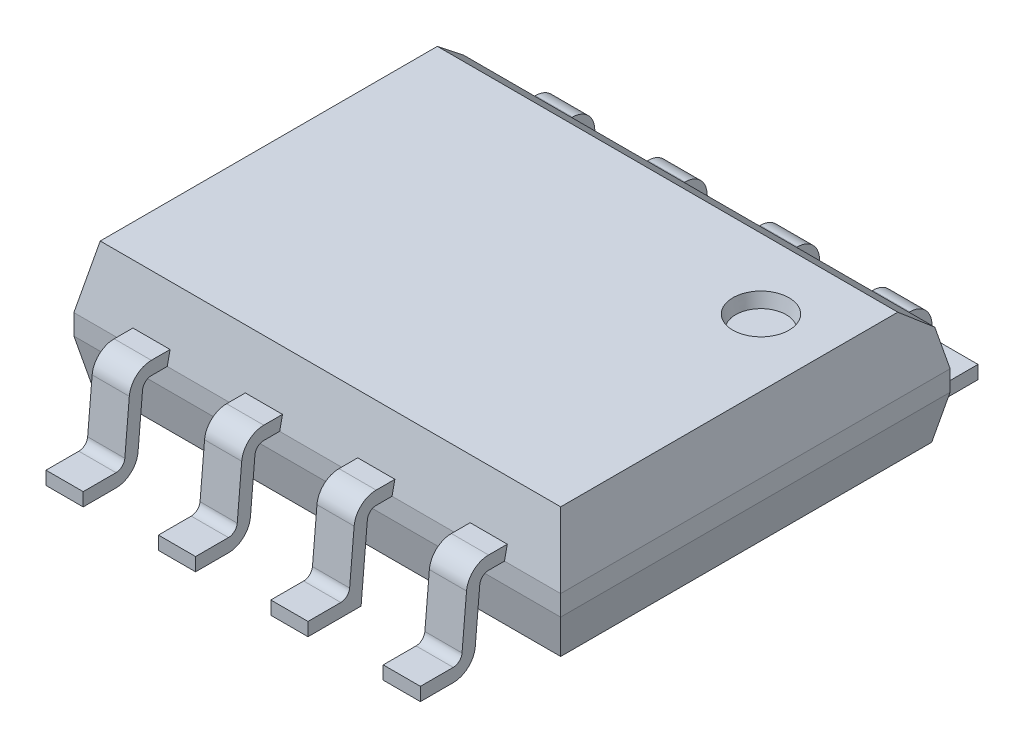
SolidWorks part; units mm, degrees
note: '?' marks a value the reader was unsure of.
ref_plane "Front Plane" through (0, 0, 0) normal (0, 0, 1) x (1, 0, 0)
ref_plane "Top Plane" through (0, 0, 0) normal (0, 1, 0) x (1, 0, 0)
ref_plane "Right Plane" through (0, 0, 0) normal (1, 0, 0) x (0, 0, -1)
ref_axis "Axis1" through (3.025, 0, 0) along (-1, 0, 0)?
sketch "Sketch1" plane through (0, 0, 0) normal (0, 1, 0) x (1, 0, 0)
  line L1 (-2.75, 2.2) -> (2.75, 2.2)
  line L2 (-2.75, 2.2) -> (-2.75, -2.2)
  line L3 (-2.75, -2.2) -> (2.75, -2.2)
  line L4 (2.75, 2.2) -> (2.75, -2.2)
  dimension "D1" = 5.5
  dimension "D2" = 4.4
  dimension "D3" = 2.75
  dimension "D4" = 2.2
extrude "Extrude1" add sketch "Sketch1" along normal blind 0.7 draft 12 and the other way blind 0.23
sketch "Sketch2" plane through (0, -0.23, 0) normal (0, -1, 0) x (1, 0, 0)
  line L4 (-2.75, 2.2) -> (-2.75, -2.2)
  line L5 (-2.75, -2.2) -> (2.75, -2.2)
  line L6 (2.75, -2.2) -> (2.75, 2.2)
  line L7 (2.75, 2.2) -> (-2.75, 2.2)
  line L8 (-2.75, 2.2) -> (-2.75, -2.2)
  line L9 (-2.75, -2.2) -> (2.75, -2.2)
  line L10 (2.75, -2.2) -> (2.75, 2.2)
  line L11 (2.75, 2.2) -> (-2.75, 2.2)
  dimension "D1" = 0
extrude "Extrude2" add sketch "Sketch2" along normal blind 0.49 draft 12
chamfer "Chamfer1" distance 0.3 angle 38.5 1 edges at (0, 0.7, -2.0512)
sketch "Sketch3" plane through (0, 0.7, 0) normal (0, 1, 0) x (-1, 0, 0)
  circle A0 centre (-1.8453, -0.9674) radius 0.3175
extrude "Cut-Extrude1" cut sketch "Sketch3" against normal blind 0.15 draft 12
sketch "Sketch4" plane through (0, 0, 0) normal (1, 0, 0) x (0, 0, -1)
  line L0 (0, 0.15) -> (0, 0)
  line L1 (-2.6874, -0.75) -> (-2.6087, 0.15)
  line L2 (-2.4713, 0) -> (2.4713, 0)
  line L3 (2.4713, 0) -> (2.55, -0.9)
  line L4 (-3.15, -0.75) -> (-2.6874, -0.75)
  line L5 (2.55, -0.9) -> (3.15, -0.9)
  line L6 (3.15, -0.9) -> (3.15, -0.75)
  line L7 (3.15, -0.75) -> (2.6874, -0.75)
  line L8 (2.6874, -0.75) -> (2.6087, 0.15)
  line L9 (2.6087, 0.15) -> (-2.6087, 0.15)
  line L10 (-3.15, -0.9) -> (-3.15, -0.75)
  line L11 (-2.55, -0.9) -> (-3.15, -0.9)
  line L12 (-2.4713, 0) -> (-2.55, -0.9)
  line L13 (2.2, 0) -> (-2.2, 0) construction
  line L14 (-2.0958, -0.72) -> (2.0958, -0.72) construction
  dimension "D1" = 0.15
  dimension "D2" = 0.15
  dimension "D3" = 0.15
  dimension "D4" = 0.6
  dimension "D5" = 6.3
  dimension "D6" = 95
  dimension "D7" = 0.18
extrude "Extrude3" add sketch "Sketch4" along normal blind 0.21 and the other way blind 0.21 from offset 0.635 contours L8 L9 L1 L4 L10 L11 L12 L2 L3 L5 L6 L7
pattern_linear "LPattern3" count 2 spacing 1.27 along (1, 0, 0) count 3 spacing 1.27 along (-1, 0, 0) of "Extrude3"
fillet "Fillet1" radius 0.1 16 edges at (1.905, -0.75, 2.6874) (0.635, -0.75, 2.6874) (-0.635, -0.75, 2.6874) (-1.905, -0.75, 2.6874) (1.905, 0, 2.4713) (0.635, 0, 2.4713) (-0.635, 0, 2.4713) (-1.905, 0, 2.4713) (1.905, -0.75, -2.6874) (0.635, -0.75, -2.6874) (-0.635, -0.75, -2.6874) (1.905, 0, -2.4713) (0.635, 0, -2.4713) (-0.635, 0, -2.4713) (-1.905, 0, -2.4713) (-1.905, -0.75, -2.6874)
fillet "Fillet2" radius 0.25 15 edges at (1.905, -0.9, 2.55) (1.905, 0.15, 2.6087) (-0.635, 0.15, 2.6087) (0.635, 0.15, 2.6087) (-0.635, -0.9, 2.55) (-1.905, -0.9, 2.55) (-1.905, 0.15, 2.6087) (1.905, 0.15, -2.6087) (0.635, 0.15, -2.6087) (-0.635, 0.15, -2.6087) (-1.905, 0.15, -2.6087) (1.905, -0.9, -2.55) (0.635, -0.9, -2.55) (-0.635, -0.9, -2.55) (-1.905, -0.9, -2.55)
ref_plane "Plane1" through (0, -0.9, 0) normal (0, 1, 0) x (-1, 0, 0)
sketch "Component_Outline" plane through (0, -0.9, 0) normal (0, 1, 0) x (-1, 0, 0)
  line L0 (2.115, 3.15) -> (2.115, 2.2)
  line L1 (-1.695, -3.15) -> (-2.115, -3.15)
  line L2 (1.695, 3.15) -> (1.695, 2.2)
  line L3 (1.695, 2.2) -> (0.845, 2.2)
  line L4 (0.845, 3.15) -> (0.845, 2.2)
  line L5 (-0.425, -3.15) -> (-0.845, -3.15)
  line L6 (0.425, 3.15) -> (0.425, 2.2)
  line L7 (0.425, 2.2) -> (-0.425, 2.2)
  line L8 (-0.425, 3.15) -> (-0.425, 2.2)
  line L9 (0.845, -3.15) -> (0.425, -3.15)
  line L10 (-0.845, 3.15) -> (-0.845, 2.2)
  line L11 (-0.845, 2.2) -> (-1.695, 2.2)
  line L12 (-1.695, 3.15) -> (-1.695, 2.2)
  line L13 (1.695, -2.2) -> (0.845, -2.2)
  line L14 (1.695, -2.2) -> (1.695, -3.15)
  line L16 (0.845, -2.2) -> (0.845, -3.15)
  line L17 (0.425, -2.2) -> (-0.425, -2.2)
  line L18 (0.425, -2.2) -> (0.425, -3.15)
  line L20 (-0.425, -2.2) -> (-0.425, -3.15)
  line L21 (-0.845, -2.2) -> (-1.695, -2.2)
  line L22 (-0.845, -2.2) -> (-0.845, -3.15)
  line L24 (-1.695, -2.2) -> (-1.695, -3.15)
  line L25 (2.115, 2.2) -> (2.75, 2.2)
  line L26 (2.75, 2.2) -> (-2.75, 2.2) construction
  line L27 (2.75, 2.2) -> (2.75, -2.2)
  line L28 (2.75, -2.2) -> (2.115, -2.2)
  line L29 (2.115, -2.2) -> (2.115, -3.15)
  line L30 (2.115, -3.15) -> (1.695, -3.15)
  line L31 (-2.115, -3.15) -> (-2.115, -2.2)
  line L32 (-2.115, -2.2) -> (-2.75, -2.2)
  line L33 (-2.75, -2.2) -> (-2.75, 2.2)
  line L34 (-2.75, 2.2) -> (-2.115, 2.2)
  line L35 (-2.115, 2.2) -> (-2.115, 3.15)
  line L36 (-2.115, 3.15) -> (-1.695, 3.15)
  line L37 (1.695, 3.15) -> (2.115, 3.15)
  line L38 (0.425, 3.15) -> (0.845, 3.15)
  line L39 (-0.845, 3.15) -> (-0.425, 3.15)
